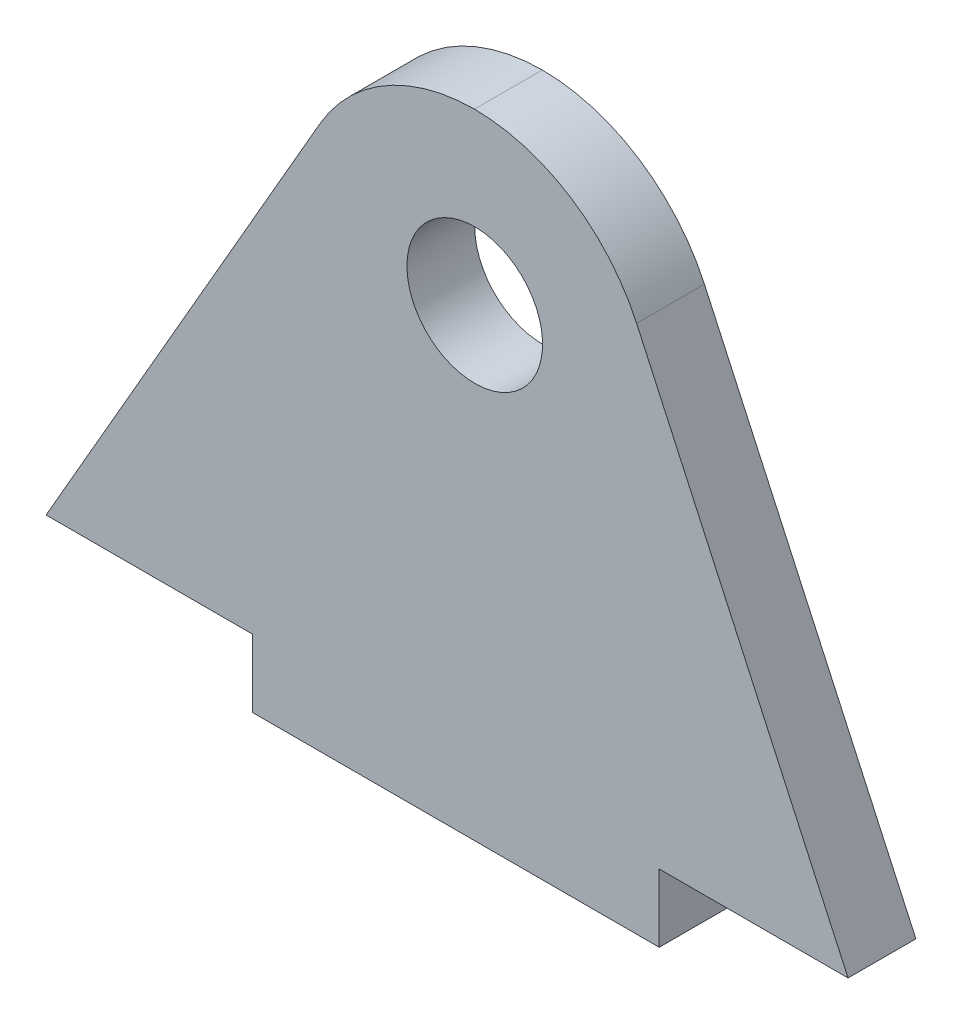
SolidWorks part; units mm, degrees
material "AISI 4340 Steel, annealed"
ref_plane "X-Y Datum" through (0, 0, 0) normal (0, 0, 1) x (1, 0, 0)
ref_plane "X-Z Datum" through (0, 0, 0) normal (0, 1, 0) x (1, 0, 0)
ref_plane "Y-Z Datum" through (0, 0, 0) normal (1, 0, 0) x (0, 0, -1)
sketch "Sketch1" plane through (0, 0, 0) normal (0, 0, 1) x (1, 0, 0)
  line L0 (0, 0) -> (0, 50000) construction
  line L1 (0, 0) -> (50000, 0) construction
  line L2 (-62.1782, 0) -> (0, 0)
  line L3 (0, 0) -> (0, 55.1596)
  line L4 (0, 55.1596) -> (-62.1782, 55.1596)
  line L5 (-62.1782, 55.1596) -> (-62.1782, 0)
  dimension "D1" = 90
  dimension "D2" = 90
  dimension "D3" = 90
  dimension "D4" = 90
extrude "Boss-Extrude1" add sketch "Sketch1" along normal blind 3.175
hole_wizard "1/4 (0.25) Diameter Hole1" positions "Sketch2" profile "Sketch3" hole size "1/4" standard "ANSI Inch" end condition through all
sketch "Sketch2" plane through (0, 0, 0) normal (0, 0, -1) x (-1, 0, 0)
  line L0 (62.1782, 0) -> (0, 0) construction
  line L1 (62.1782, 55.1596) -> (62.1782, 0) construction
  point P0 (42.1122, 18.542)
  dimension "D1" = 18.542
  dimension "D2" = 20.066
sketch "Sketch3" plane through (-42.1122, 18.542, 0) normal (1, 0, 0) x (0, 1, 0)
  line L0 (0, 0) -> (0, 3.175)
  line L1 (0, 3.175) -> (3.175, 3.175)
  line L2 (3.175, 3.175) -> (3.175, 0)
  line L5 (3.175, 0) -> (0, 0)
  line L11 (0, -78.8889) -> (0, 107.95) construction
  dimension "Thru Hole Dia." = 6.35
  dimension "Thru Hole Depth" = 3.175
sketch "Sketch4" plane through (0, 0, 0) normal (0, 0, -1) x (-1, 0, 0)
  line L0 (62.1782, 0) -> (46.9382, 26.4795)
  line L1 (62.1782, 0) -> (0, 0) construction
  line L2 (46.9382, 26.4795) -> (36.7782, 26.4795)
  line L3 (36.7782, 26.4795) -> (24.637, 0)
  line L4 (24.637, 0) -> (62.1782, 0)
  line M6 (62.1782, 0) -> (62.1782, 55.1596)
  line M7 (62.1782, 55.1596) -> (0, 55.1596)
  line M8 (0, 55.1596) -> (0, 0)
  line M9 (0, 0) -> (62.1782, 0)
  dimension "D1" = 37.5412
  dimension "D2" = 15.24
  dimension "D3" = 26.4795
  dimension "D4" = 10.16
extrude "Cut-Extrude6" cut sketch "Sketch4" against normal through all contours L3 L2 L0 M6 M7 M8 M9 region at (-28.4502, 31.3881, 0)
fillet "Fillet1" radius 8.382 2 edges at (-46.9382, 26.4795, 1.5875) (-36.7782, 26.4795, 1.5875)
sketch "Sketch7" plane through (0, 0, 0) normal (0, 0, -1) x (-1, 0, 0)
  line L0 (33.4762, 0) -> (33.4762, -3.175)
  line L1 (62.1782, 0) -> (24.637, 0) construction
  line L2 (33.4762, -3.175) -> (52.5262, -3.175)
  line L3 (52.5262, -3.175) -> (52.5262, 0)
  line L4 (52.5262, 0) -> (33.4762, 0)
  dimension "D1" = 3.175
  dimension "D2" = 19.05
  dimension "D3" = 9.652
extrude "Boss-Extrude2" add sketch "Sketch7" against normal blind 3.175
